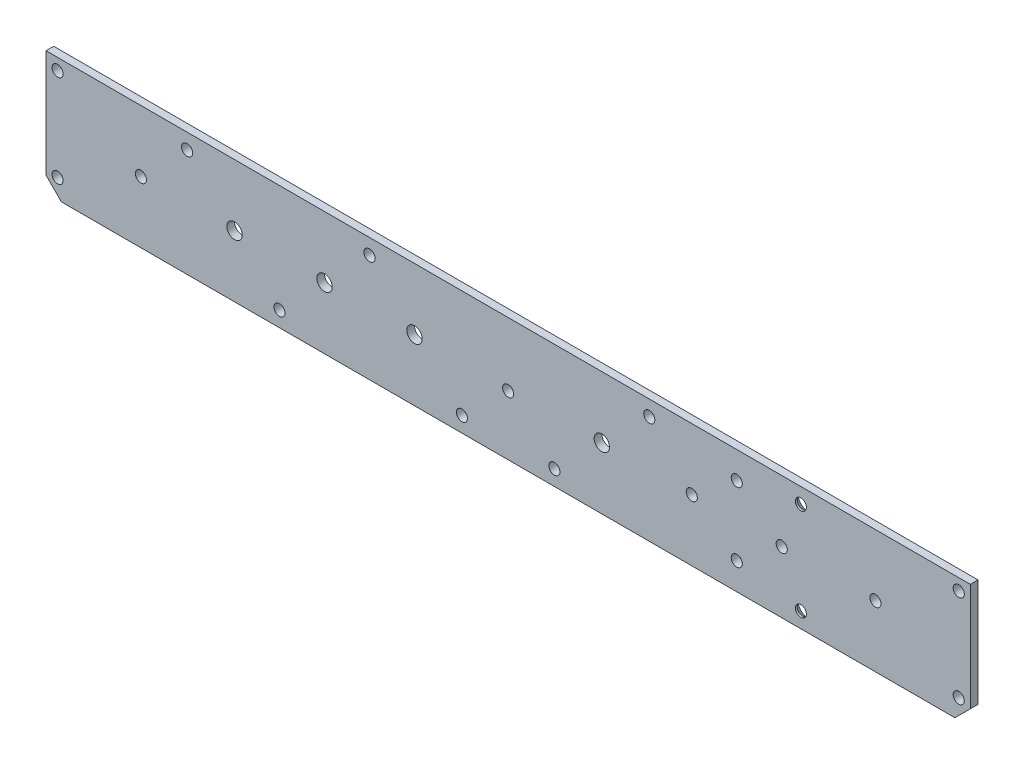
SolidWorks part; units mm, degrees
ref_plane "Front Plane" through (0, 0, 0) normal (0, 0, 1) x (1, 0, 0)
ref_plane "Top Plane" through (0, 0, 0) normal (0, 1, 0) x (1, 0, 0)
ref_plane "Right Plane" through (0, 0, 0) normal (1, 0, 0) x (0, 0, -1)
sketch "Sketch1" plane through (0, 0, 0) normal (0, 0, 1) x (1, 0, 0)
  line L1 (0, 0) -> (381, 0)
  line L2 (0, 0) -> (0, 50.8)
  line L3 (0, 50.8) -> (381, 50.8)
  line L4 (381, 0) -> (381, 50.8)
  dimension "D1" = 50.8
  dimension "D2" = 381
extrude "Boss-Extrude1" add sketch "Sketch1" along normal blind 3.175
sketch "Sketch2" plane through (0, 0, 3.175) normal (0, 0, 1) x (1, 0, 0)
  line L0 (77.724, 25.4) -> (114.808, 25.4) construction
  line L1 (190.5, 50.8) -> (190.5, 0) construction
  line L2 (381, 50.8) -> (0, 50.8) construction
  line L3 (0, 0) -> (381, 0) construction
  line L4 (266.192, 25.4) -> (303.276, 25.4) construction
  line L5 (0, 6.35) -> (0, 0)
  line L6 (0, 50.8) -> (0, 0) construction
  line L7 (0, 0) -> (6.35, 0)
  line L8 (6.35, 0) -> (0, 6.35)
  line L9 (381, 0) -> (374.65, 0)
  line L10 (374.65, 0) -> (381, 6.35)
  line L11 (381, 6.35) -> (381, 0)
  line L12 (381, 0) -> (381, 50.8) construction
  circle A0 centre (39.116, 25.4) radius 2.286
  circle A1 centre (190.5, 24.6062) radius 2.286
  circle A2 centre (114.808, 25.4) radius 3.175
  circle A3 centre (77.724, 25.4) radius 3.175
  circle A4 centre (151.892, 25.4) radius 3.175
  circle A5 centre (229.108, 25.4) radius 3.175
  circle A6 centre (303.276, 25.4) radius 2.286
  circle A7 centre (266.192, 25.4) radius 2.286
  circle A8 centre (341.884, 25.4) radius 2.286
  circle A9 centre (58.166, 44.45) radius 2.286
  circle A10 centre (171.45, 6.35) radius 2.286
  circle A11 centre (209.55, 6.35) radius 2.286
  circle A13 centre (133.35, 44.45) radius 2.286
  circle A14 centre (248.666, 44.45) radius 2.286
  circle A15 centre (96.266, 6.35) radius 2.286
  circle A19 centre (4.7625, 46.0375) radius 2.286
  circle A20 centre (4.7625, 7.9375) radius 2.286
  circle A21 centre (376.2375, 7.9375) radius 2.286
  circle A22 centre (376.2375, 46.0375) radius 2.286
  circle A24 centre (311.15, 44.45) radius 2.286
  circle A25 centre (284.734, 11.1125) radius 2.286
  circle A26 centre (284.734, 39.6875) radius 2.286
  circle A27 centre (311.15, 6.35) radius 2.286
  point P17 (190.5, 25.4)
  point P38 (96.266, 25.4)
  point P49 (284.734, 25.4)
  point P66 (0, 0)
  dimension "D2" = 4.572
  dimension "D5" = 6.35
  dimension "D7" = 4.572
  dimension "D12" = 4.572
  dimension "D15" = 4.572
  dimension "D16" = 4.572
  dimension "D19" = 4.572
  dimension "D21" = 6.35
  dimension "D27" = 4.572
  dimension "D29" = 11.1125
  dimension "D8" = 4.572
  dimension "D10" = 4.572
  dimension "D13" = 6.35
  dimension "D3" = 38.608
  dimension "D4" = 0.7937
  dimension "D6" = 14.2875
  dimension "D9" = 69.85
  dimension "D11" = 6.35
  dimension "D22" = 6.35
  dimension "D25" = 4.7625
  dimension "D26" = 4.7625
  dimension "D28" = 7.9375
extrude "Cut-Extrude1" cut sketch "Sketch2" against normal up to next (3.175 mm away)
chamfer "Chamfer1" distance 2.3813 angle 41 2 edges at (308.864, 44.45, 0) (308.864, 6.35, 0) first distance on face at (308.864, 44.45, 0) first distance on face at (308.864, 6.35, 0)
